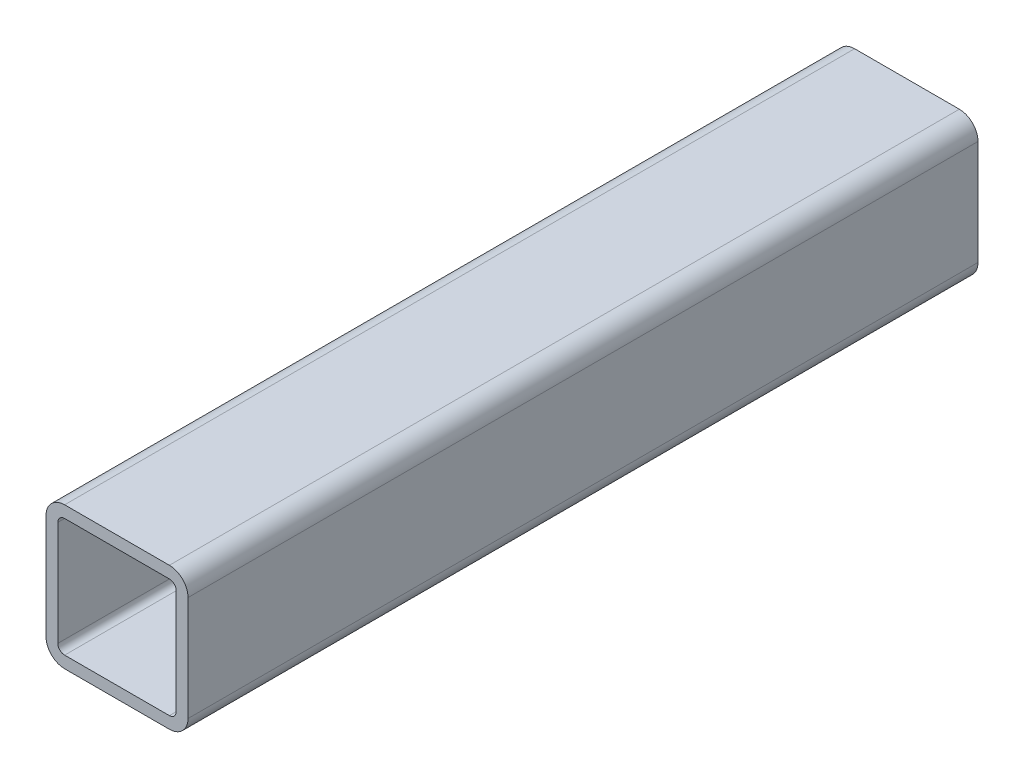
SolidWorks part; units mm, degrees
ref_plane "Front Plane" through (0, 0, 0) normal (0, 0, 1) x (1, 0, 0)
ref_plane "Top Plane" through (0, 0, 0) normal (0, 1, 0) x (1, 0, 0)
ref_plane "Right Plane" through (0, 0, 0) normal (1, 0, 0) x (0, 0, -1)
sketch "Sketch1" plane through (0, 0, 0) normal (0, 0, 1) x (1, 0, 0)
  line L7 (-14.05, 19.05) -> (14.05, 19.05)
  line L8 (19.05, 14.05) -> (19.05, -14.05)
  line L9 (-15.875, 14.05) -> (-15.875, -14.05)
  line L10 (-14.05, -15.875) -> (14.05, -15.875)
  line L11 (14.05, -19.05) -> (-14.05, -19.05)
  line L12 (-19.05, -14.05) -> (-19.05, 14.05)
  line L13 (0, 19.05) -> (0, -19.05) construction
  line L14 (-19.05, 0) -> (19.05, 0) construction
  line L15 (15.875, -14.05) -> (15.875, 14.05)
  line L16 (14.05, 15.875) -> (-14.05, 15.875)
  line L17 (0, 15.875) -> (0, -15.875) construction
  line L18 (-15.875, 0) -> (15.875, 0) construction
  arc A0 (14.05, 19.05) -> (19.05, 14.05) centre (14.05, 14.05) cw
  arc A1 (19.05, -14.05) -> (14.05, -19.05) centre (14.05, -14.05) cw
  arc A2 (-14.05, -19.05) -> (-19.05, -14.05) centre (-14.05, -14.05) cw
  arc A3 (-19.05, 14.05) -> (-14.05, 19.05) centre (-14.05, 14.05) cw
  arc A4 (-15.875, -14.05) -> (-14.05, -15.875) centre (-14.05, -14.05) ccw
  arc A5 (14.05, -15.875) -> (15.875, -14.05) centre (14.05, -14.05) ccw
  arc A6 (15.875, 14.05) -> (14.05, 15.875) centre (14.05, 14.05) ccw
  arc A7 (-14.05, 15.875) -> (-15.875, 14.05) centre (-14.05, 14.05) ccw
  point P39 (0, 0)
  dimension "D1" = 5
  dimension "D2" = 38.1
  dimension "D3" = 3.175
extrude "Boss-Extrude1" add sketch "Sketch1" along normal blind 211.9
